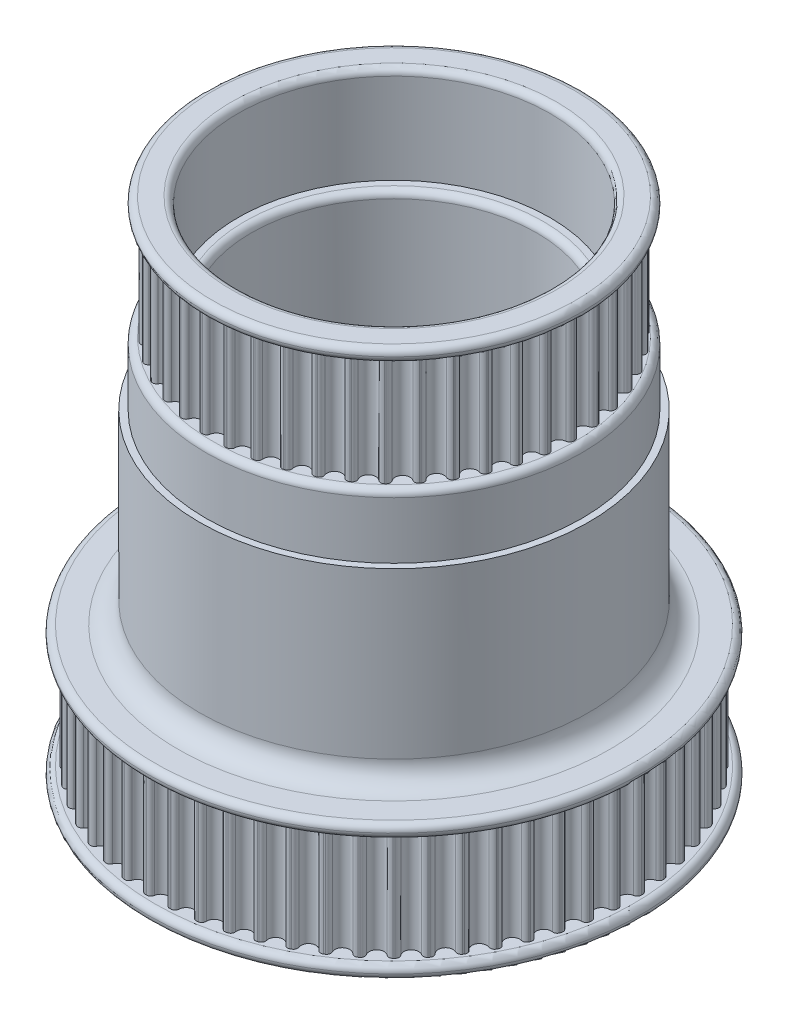
SolidWorks part; units mm, degrees
ref_plane "Front Plane" through (0, 0, 0) normal (0, 0, 1) x (1, 0, 0)
ref_plane "Top Plane" through (0, 0, 0) normal (0, 1, 0) x (1, 0, 0)
ref_plane "Right Plane" through (0, 0, 0) normal (1, 0, 0) x (0, 0, -1)
sketch "PulleyOffsets" plane through (0, 0, 0) normal (1, 0, 0) x (0, 0, -1)
  line L0 (22.225, 0) -> (-22.225, 0) construction
  line L1 (22.225, 44.45) -> (-22.225, 44.45) construction
  line L2 (0, 0) -> (0, 44.45) construction
  point P7 (0, 0)
  dimension "D1" = 44.45
ref_axis "Axis1" through (0, 34.9332, 0) along (0, -1, 0)
ref_plane "Big Pulley Plane" through (0, 0, 0) normal (0, 1, 0) x (1, 0, 0)
ref_plane "Small Pulley Plane" through (0, 44.45, 0) normal (0, 1, 0) x (1, 0, 0)
sketch "Sketch1" plane through (0, 0, 0) normal (0, 1, 0) x (1, 0, 0)
  line L0 (0, 0) -> (0, 28.2667) construction
  line L1 (0, 0) -> (2.9202, 27.7837) construction
  circle A0 centre (0, 0) radius 28.2667 construction
  circle A1 centre (0, 0) radius 27.0467 construction
  circle A2 centre (0, 27.9367) radius 0.89 construction
  circle A5 centre (2.9202, 27.7837) radius 0.89 construction
  arc A6 (0, 27.0467) -> (0.8804, 27.8061) centre (0, 27.9367) ccw
  arc A7 (0.8804, 27.8061) -> (1.3997, 28.2321) centre (1.3749, 27.7327) cw
  arc A8 (1.559, 28.2237) -> (2.031, 27.7458) centre (1.5314, 27.7245) cw
  arc A9 (2.8272, 26.8986) -> (2.031, 27.7458) centre (2.9202, 27.7837) cw
  arc A10 (1.3997, 28.2321) -> (1.559, 28.2237) centre (0, 0) cw
  arc A11 (0, 27.0467) -> (2.8272, 26.8986) centre (0, 0) ccw
  dimension "D1" = 56.5335
  dimension "D3" = 1.78
  dimension "D4" = 0.5
  dimension "D2" = 1.22
  dimension "D5" = 6
extrude "Boss-Extrude1" add sketch "Sketch1" along normal mid plane 13 contours A6 A11 A9 A8 A7 region at (0.001, 0, -0.0192)
pattern_circular "CirPattern1" count 60 over 360 about axis through (0, 34.9332, 0) along (0, -1, 0) of "Boss-Extrude1"
sketch "Sketch2" plane through (0, 0, 0) normal (1, 0, 0) x (0, 0, -1)
  line L10 (0, 6.5) -> (29.4415, 6.5) construction
  line L11 (0, 6.5) -> (0, 8.0875) construction
  line L12 (0, 8.0875) -> (29.4415, 8.0875) construction
  line L15 (29.4415, 6.5) -> (29.4415, 8.0875) construction
  line L20 (0, 34.9332) -> (0, -6.9932) construction
  line L22 (29.4415, 8.0875) -> (0, 8.0875)
  line L23 (29.4415, 8.0875) -> (29.4415, 6.5)
  line L24 (29.4415, 6.5) -> (0, 6.5)
  line L25 (0, 8.0875) -> (0, 6.5)
  dimension "D1" = 1.5875
  dimension "D2" = 29.4415
  dimension "D3" = 6.5
revolve "Revolve3" add sketch "Sketch2" angle 360 about axis through (0, 34.9332, 0) along (0, -1, 0) region at (0, 7.2937, -14.7207)
mirror "Mirror1" about plane through (0, 0, 0) normal (0, 1, 0) of "Revolve3"
sketch "Sketch6" plane through (0, 0, 0) normal (0, 1, 0) x (1, 0, 0)
  line L0 (0, 0) -> (0, 21.582) construction
  line L1 (0, 0) -> (2.8938, 21.0541) construction
  circle A0 centre (0, 0) radius 21.582 construction
  circle A1 centre (0, 0) radius 20.362 construction
  circle A2 centre (0, 21.252) radius 0.89 construction
  circle A5 centre (2.8938, 21.0541) radius 0.89 construction
  arc A6 (0, 20.362) -> (0.8793, 21.1145) centre (0, 21.252) ccw
  arc A7 (0.8793, 21.1145) -> (1.4059, 21.5362) centre (1.3733, 21.0373) cw
  arc A8 (1.5397, 21.527) -> (2.004, 21.0376) centre (1.5041, 21.0283) cw
  arc A9 (2.7726, 20.1724) -> (2.004, 21.0376) centre (2.8938, 21.0541) cw
  arc A10 (1.4059, 21.5362) -> (1.5397, 21.527) centre (0, 0) cw construction
  arc A11 (0, 20.362) -> (2.7726, 20.1724) centre (0, 0) ccw
  arc A12 (1.4059, 21.5362) -> (1.5397, 21.527) centre (0, 0) cw
  dimension "D3" = 1.78
  dimension "D4" = 0.5
  dimension "D2" = 1.22
  dimension "D1" = 43.1641
  dimension "D5" = 7.826
extrude "Boss-Extrude2" add sketch "Sketch6" along normal mid plane 13 from surface contours A6 A11 A9 A8 A7 region at (0.0017, 0, -0.025) starting at plane "Small Pulley Plane"
pattern_circular "CirPattern2" count 46 over 360 about axis through (0, 34.9332, 0) along (0, -1, 0) of "Boss-Extrude2"
sketch "Sketch9" plane through (0, 0, 0) normal (1, 0, 0) x (0, 0, -1)
  line L1 (0, 37.95) -> (22.7568, 37.95)
  line L2 (0, 37.95) -> (0, 36.3625)
  line L3 (0, 36.3625) -> (22.7568, 36.3625)
  line L4 (22.7568, 37.95) -> (22.7568, 36.3625)
  line L6 (0, 50.95) -> (22.7568, 50.95)
  line L7 (0, 50.95) -> (0, 52.5375)
  line L8 (0, 52.5375) -> (22.7568, 52.5375)
  line L9 (22.7568, 50.95) -> (22.7568, 52.5375)
  line L10 (29.4415, 8.0875) -> (29.4415, 6.5) construction
  line L11 (0, 34.9332) -> (0, -6.9932) construction
  line L12 (21.1145, 50.95) -> (20.362, 50.95) construction
  line L13 (20.1641, 37.95) -> (21.0376, 37.95) construction
  dimension "D1" = 22.7568
revolve "Revolve4" add sketch "Sketch9" angle 360 about axis through (0, 34.9332, 0) along (0, -1, 0)
sketch "Sketch10" plane through (0, -8.0875, 0) normal (0, -1, 0) x (1, 0, 0)
  circle A0 centre (0, 0) radius 18.669
  dimension "D1" = 37.338
extrude "Cut-Extrude1" cut sketch "Sketch10" against normal through all
sketch "Sketch11" plane through (0, 52.5375, 0) normal (0, 1, 0) x (1, 0, 0)
  circle A0 centre (0, 0) radius 22.5
  dimension "D1" = 45
extrude "Cut-Extrude2" cut sketch "Sketch11" against normal up to surface (16.175 mm away) flip side to cut up to face at (0, 36.3625, 18.669)
sketch "Sketch12" plane through (0, 0, 0) normal (0, 0, 1) x (1, 0, 0)
  line L0 (29.4415, 8.0875) -> (-29.4415, 8.0875) construction
  line L1 (18.669, 36.3625) -> (22.5, 36.3625)
  line L2 (18.669, 36.3625) -> (18.669, 8.0875) construction
  line L3 (18.669, 8.0875) -> (22.5, 8.0875)
  line L4 (22.5, 36.3625) -> (22.5, 8.0875) construction
  line L5 (22.5, 36.3625) -> (22.5, 37.95) construction
  line L6 (22.5, 30.3625) -> (22.5, 36.3625)
  line L7 (22.5, 30.3625) -> (23.2938, 30.3625)
  line L8 (22.5, 30.3625) -> (22.5, 8.0875) construction
  line L9 (22.5, 8.0875) -> (23.2938, 8.0875)
  line L10 (23.2938, 30.3625) -> (23.2938, 8.0875)
  line L11 (18.669, -8.0875) -> (18.669, 8.0875) construction
  line L12 (18.669, 2.0875) -> (17.0815, 2.0875)
  line L13 (18.669, 2.0875) -> (18.669, 40.95) construction
  line L14 (18.669, 40.95) -> (17.0815, 40.95)
  line L15 (17.0815, 2.0875) -> (17.0815, 40.95)
  line L16 (-29.4415, -8.0875) -> (29.4415, -8.0875) construction
  line L18 (18.669, 2.0875) -> (18.669, 8.0875)
  line L19 (18.669, 36.3625) -> (18.669, 40.95)
  line L20 (32.3856, 44.45) -> (-32.3856, 44.45) construction
  dimension "D1" = 6
  dimension "D2" = 0.7937
  dimension "D3" = 10.175
  dimension "D5" = 1.5875
  dimension "D4" = 3.5
revolve "Revolve5" add sketch "Sketch12" angle 360 about axis through (0, 34.9332, 0) along (0, -1, 0)
fillet "Fillet1" radius 2.54 1 edges at (0, 8.0875, -23.2938)
fillet "Fillet2" radius 0.7937 11 edges at (0, 40.95, 17.0815) (0, 52.5375, -18.669) (0, -8.0875, -18.669) (0, 2.0875, 17.0815) (0, -8.0875, 29.4415) (0, 8.0875, 29.4415) (0, 52.5375, 22.5) (0, 50.95, 22.5) (0, 37.95, -22.5) (0, 6.5, 29.4415) (0, -6.5, 29.4415)
equation "\"TEETH_NUM\"= 60"
equation "\"TOOTH_PITCH\"= 3mm"
equation "\"PITCH_LINE_OFFSET\"= .015in"
equation "\"DIAMETER_PER_GROOVE\"= \"OUTSIDE_DIAMETER\" / \"TEETH_NUM\" * 1in"
equation "\"PITCH_DIAMETER\"= ( ( \"TEETH_NUM\" * 3 - 1.31 ) / 3.1415 + .415 ) * 1mm"
equation "\"OUTSIDE_DIAMETER\"= \"PITCH_DIAMETER\" - \"PITCH_LINE_OFFSET\" * 2"
equation "\"D1@Sketch1\"=\"OUTSIDE_DIAMETER\""
equation "\"TOOTH_HEIGHT\"= 1.22mm"
equation "\"D2@Sketch1\"=\"TOOTH_HEIGHT\""
equation "\"TOOTH_DIAMETER\"= 1.78mm"
equation "\"INTERNAL_RADIUS\"= .5mm"
equation "\"D3@Sketch1\"=\"TOOTH_DIAMETER\""
equation "\"D5@Sketch1\"=360 / \"TEETH_NUM\""
equation "\"D4@Sketch1\"=\"INTERNAL_RADIUS\""
equation "\"D1@CirPattern1\"=\"TEETH_NUM\""
equation "\"BELT_GAP\"= 13mm"
equation "\"D2@Sketch2\"=\"PITCH_DIAMETER\"/2+1/32"
equation "\"D3@Sketch2\"=\"BELT_GAP\"/2"
equation "\"2_TEETH_NUM\"= 46"
equation "\"2_PITCH_DIAMETER\"= ( ( \"2_TEETH_NUM\" * 3 - 1.31 ) / 3.1415 + .415 ) * 1mm"
equation "\"2_OUTSIDE_DIAMETER\"= \"2_PITCH_DIAMETER\" - \"PITCH_LINE_OFFSET\" * 2"
equation "\"2_DIAMETER_PER_GROOVE\"= \"2_OUTSIDE_DIAMETER\" / \"2_TEETH_NUM\" * 1in"
equation "\"D5@Sketch6\"=360/\"2_TEETH_NUM\""
equation "\"D1@Sketch6\"=\"2_OUTSIDE_DIAMETER\""
equation "\"D2@Sketch6\"=\"TOOTH_HEIGHT\""
equation "\"D3@Sketch6\"=\"TOOTH_DIAMETER\""
equation "\"D4@Sketch6\"=\"INTERNAL_RADIUS\""
equation "\"2_BELT_GAP\"= 13mm"
equation "\"D1@CirPattern2\"=\"2_TEETH_NUM\""
equation "\"D1@Boss-Extrude2\"=\"2_BELT_GAP\""
equation "\"Pulley_OffSets\"= 1.75"
equation "\"D1@PulleyOffsets\" = \"Pulley_OffSets\""
equation "\"D1@Boss-Extrude1\"=\"BELT_GAP\""
equation "\"D1@Sketch9\"=\"2_PITCH_DIAMETER\"/2+1/32"
equation "\"bearing_hole_depth_arm_side\"= 7mm + .125in"
equation "\"D3@Sketch12\"=\"bearing_hole_depth_arm_side\""
